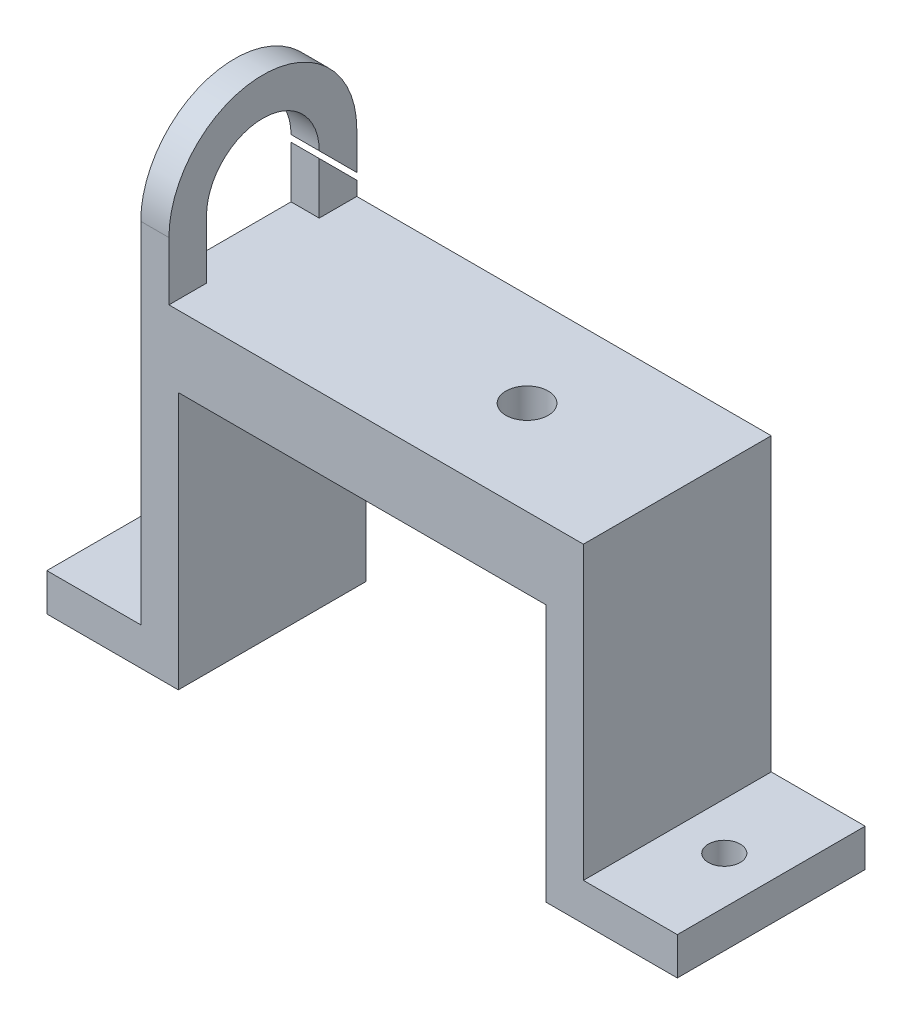
SolidWorks part; units mm, degrees
material "Onyx w/ CF"
ref_plane "Front Plane" through (0, 0, 0) normal (0, 0, 1) x (1, 0, 0)
ref_plane "Top Plane" through (0, 0, 0) normal (0, 1, 0) x (1, 0, 0)
ref_plane "Right Plane" through (0, 0, 0) normal (1, 0, 0) x (0, 0, -1)
sketch "Sketch1" plane through (0, 0, 0) normal (0, 0, 1) x (1, 0, 0)
  line L0 (-19.5635, 0) -> (19.5635, 0)
  line L1 (-19.5635, 0) -> (-19.5635, -31)
  line L2 (19.5635, 0) -> (19.5635, -31)
  line L3 (-19.5635, -31) -> (-33.5635, -31)
  line L4 (-33.5635, -31) -> (-33.5635, -27)
  line L5 (-33.5635, -27) -> (-23.5635, -27)
  line L6 (-23.5635, -27) -> (-23.5635, 4)
  line L7 (-23.5635, 4) -> (23.5635, 4)
  line L8 (23.5635, 4) -> (23.5635, -27)
  line L9 (23.5635, -27) -> (33.5635, -27)
  line L10 (33.5635, -27) -> (33.5635, -31)
  line L11 (33.5635, -31) -> (19.5635, -31)
  point P3 (0, 0)
  point P13 (0, 0)
  point P15 (-34.2349, -16.0715)
  point P16 (-19.5635, -18.3263)
  point P17 (0, 0)
  dimension "D1" = 39.127
  dimension "D2" = 31
  dimension "D3" = 4
  dimension "D4" = 4
  dimension "D5" = 10
  dimension "D6" = 4
extrude "Boss-Extrude1" add sketch "Sketch1" along normal mid plane 20
sketch "Sketch2" plane through (0, 0, 0) normal (1, 0, 0) x (0, 0, -1)
  line L0 (-10, 0) -> (10, 0) construction
  line L1 (-10, 4) -> (-10, -27) construction
  line L2 (10, 4) -> (10, -27) construction
  line L3 (-10, 0) -> (10, 0)
  line L4 (10, -3.5819) -> (10, 0)
  line L5 (-10, -3.5819) -> (-10, 0)
  arc A0 (-10, -3.5819) -> (10, -3.5819) centre (0, -15.75) cw
  dimension "D1" = 15.75
extrude "Boss-Extrude2" add sketch "Sketch2" along normal up to surface (19.5635 mm away) from surface contours L5 A0 L3 | L3 A0 L4 region at (0, -1.0498, -7.5604) region at (0, -1.0498, 7.5604) up to face at (19.5635, -15.5, 0) starting at face at (-19.5635, -15.5, 0)
hole_wizard "M3 Clearance Hole1" positions "Sketch3" profile "Sketch4" hole size "M3" standard "ANSI Metric"
sketch "Sketch3" plane through (0, -27, 0) normal (0, 1, 0) x (1, 0, 0)
  line L0 (-23.5635, 10) -> (-33.5635, 10) construction
  line L1 (33.5635, 10) -> (23.5635, 10) construction
  line L2 (33.5635, -10) -> (33.5635, 10) construction
  point P0 (28.5635, 0)
  point P2 (28.5635, 0)
  point P4 (-28.5635, 0)
  point P9 (-28.5635, 10)
  point P12 (28.5635, 10)
  point P15 (33.5635, 0)
sketch "Sketch4" plane through (28.5635, -27, 0) normal (1, 0, 0) x (0, 0, 1)
  line L0 (0, 0) -> (0, 8.5215)
  line L1 (0, 8.5215) -> (1.7, 7.5)
  line L2 (1.7, 7.5) -> (1.7, 0)
  line L5 (1.7, 0) -> (0, 0)
  line L10 (0, 8.5215) -> (-1.7, 7.5) construction
  line L11 (0, -6.35) -> (0, 107.95) construction
  dimension "Hole Dia." = 3.4
  dimension "Hole Depth" = 7.5
  dimension "Drill Angle" = 118
hole_wizard "M4 Clearance Hole1" positions "Sketch5" profile "Sketch6" hole size "M4" standard "ANSI Metric" end condition through all
sketch "Sketch5" plane through (0, 4, 0) normal (0, 1, 0) x (1, 0, 0)
  line L0 (19.5635, 10) -> (19.5635, -10) construction
  point P0 (7.5635, 0)
  point P3 (0, 0)
  dimension "D1" = 12
sketch "Sketch6" plane through (7.5635, 4, 0) normal (1, 0, 0) x (0, 0, 1)
  line L0 (0, 0) -> (0, 35)
  line L1 (0, 35) -> (2.25, 35)
  line L2 (2.25, 35) -> (2.25, 0)
  line L5 (2.25, 0) -> (0, 0)
  line L11 (0, -6.35) -> (0, 107.95) construction
  dimension "Thru Hole Dia." = 4.5
  dimension "Thru Hole Depth" = 35
sketch "Sketch7" plane through (-23.5635, 0, 0) normal (-1, 0, 0) x (0, 0, 1)
  line L0 (-10, 4) -> (-10, 5.5)
  line L1 (10, 4) -> (-10, 4) construction
  line L2 (-10, 5.5) -> (-6, 9.5)
  line L3 (-6, 9.5) -> (-6, 4)
  line L4 (-6, 4) -> (-10, 4)
  line L5 (-10, 6.2071) -> (-6, 10.2071)
  line L6 (10, 4) -> (10, 10.2071)
  line L7 (10, 4) -> (10, -27) construction
  line L8 (10, 4) -> (6, 4)
  line L9 (6, 4) -> (6, 10.2071)
  line L10 (-10, 6.2071) -> (-10, 10.2071)
  arc A0 (6, 10.2071) -> (-6, 10.2071) centre (0, 10.2071) ccw
  arc A1 (10, 10.2071) -> (-10, 10.2071) centre (0, 10.2071) ccw
  point P18 (0, 0)
  point P19 (-6, 12.0418)
  point P20 (0, 0)
  point P21 (-6, 10.9598)
  point P22 (-6, 10.0861)
  point P23 (-10, 8.7159)
  point P24 (0, 0)
  point P25 (-6, 9.8221)
  point P26 (0, 16.2071)
  point P27 (0, 20.2071)
  point P28 (-6, 10.3183)
  dimension "D3" = 0.5
  dimension "D1" = 4
  dimension "D2" = 45
  dimension "D4" = 4
  dimension "D5" = 1.5
extrude "Boss-Extrude3" add sketch "Sketch7" against normal blind 3
